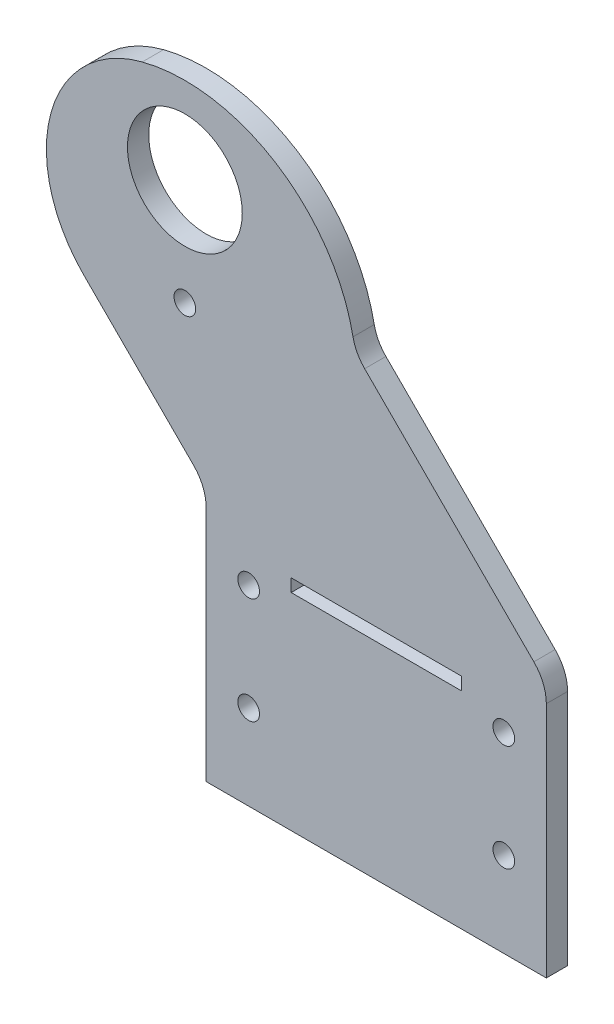
SolidWorks part; units mm, degrees
ref_plane "正面" through (0, 0, 0) normal (0, 0, 1) x (1, 0, 0)
ref_plane "平面" through (0, 0, 0) normal (0, 1, 0) x (1, 0, 0)
ref_plane "右側面" through (0, 0, 0) normal (1, 0, 0) x (0, 0, -1)
sketch "ｽｹｯﾁ1" plane through (0, 0, 0) normal (0, 0, 1) x (1, 0, 0)
  line L0 (-85, -71.4) -> (-85, -11.4) construction
  line L1 (-85, -11.4) -> (-40, 33.6) construction
  line L2 (-40, 33.6) -> (40, 33.6) construction
  line L3 (40, 33.6) -> (85, -11.4)
  line L4 (85, -11.4) -> (85, -71.4)
  line L5 (85, -71.4) -> (-85, -71.4) construction
  line L6 (40, 33.6) -> (-85, -71.4) construction
  line L7 (-40, 33.6) -> (85, -71.4) construction
  line L8 (0, 0) -> (0, -18.9) construction
  line L9 (-75, -61.4) -> (75, -61.4) construction
  line L10 (-75, -61.4) -> (-75, 23.6) construction
  line L11 (-75, 23.6) -> (75, 23.6) construction
  line L12 (75, -61.4) -> (75, 23.6) construction
  line L13 (-75, -61.4) -> (75, 23.6) construction
  line L14 (-75, 23.6) -> (75, -61.4) construction
  line L15 (0, 48.6) -> (0, 0) construction
  line L16 (-40, 33.6) -> (5, -11.4)
  line L17 (5, -11.4) -> (5, -71.4)
  line L18 (5, -71.4) -> (85, -71.4)
  circle A0 centre (75, -26.4) radius 2.55
  circle A1 centre (75, -51.4) radius 2.55
  circle A2 centre (-75, -26.4) radius 2.55 construction
  circle A3 centre (-75, -51.4) radius 2.55 construction
  circle A4 centre (0, 23.6) radius 2.55
  arc A5 (-40, 33.6) -> (40, 33.6) centre (0, 28.6) cw
  circle A6 centre (0, 48.6) radius 13.5
  point P2 (0, 0)
  point P10 (0, -18.9)
  dimension "D9" = 20
  dimension "D13" = 5.1
  dimension "D14" = 5
  dimension "D15" = 27
  dimension "D1" = 170
  dimension "D2" = 45
  dimension "D3" = 45
  dimension "D4" = 80
  dimension "D5" = 60
  dimension "D6" = 10
  dimension "D7" = 10
  dimension "D8" = 10
  dimension "D10" = 25
  dimension "D11" = 20
  dimension "D12" = 25
  dimension "D16" = 15
  dimension "D17" = 80
extrude "ﾎﾞｽ - 押し出し1" add sketch "ｽｹｯﾁ1" along normal blind 5
fillet "ﾌｨﾚｯﾄ1" radius 10 3 edges at (85, -11.4, 2.5) (40, 33.6, 2.5) (5, -11.4, 2.5)
sketch "ｽｹｯﾁ2" plane through (0, 0, 5) normal (0, 0, 1) x (1, 0, 0)
  line L0 (15, -71.4) -> (15, -10.4721) construction
  line L1 (5, -71.4) -> (85, -71.4) construction
  line L2 (5, -15.5421) -> (5, -71.4) construction
  line L3 (75, -26.4) -> (15, -26.4) construction
  line L4 (75, -51.4) -> (15, -51.4) construction
  circle A0 centre (15, -51.4) radius 2.55
  circle A1 centre (15, -26.4) radius 2.55
  circle A2 centre (75, -51.4) radius 2.55 construction
  dimension "D1" = 10
extrude "ｶｯﾄ - 押し出し1" cut sketch "ｽｹｯﾁ2" against normal through all
fillet "ﾌｨﾚｯﾄ2" radius 30 1 edges at (-40, 33.6, 2.5)
sketch "ｽｹｯﾁ3" plane through (0, 0, 0) normal (0, 0, -1) x (-1, 0, 0)
  line L0 (-45, -71.4) -> (-45, -21.4) construction
  line L1 (-65, -19.9) -> (-25, -19.9)
  line L2 (-65, -19.9) -> (-65, -22.9)
  line L3 (-65, -22.9) -> (-25, -22.9)
  line L4 (-25, -19.9) -> (-25, -22.9)
  line L5 (-65, -19.9) -> (-25, -22.9) construction
  line L6 (-65, -22.9) -> (-25, -19.9) construction
  line L7 (-5, -71.4) -> (-85, -71.4) construction
  point P0 (-45, -21.4)
  dimension "D1" = 3
  dimension "D2" = 40
  dimension "D3" = 50
extrude "ｶｯﾄ - 押し出し2" cut sketch "ｽｹｯﾁ3" against normal through all
